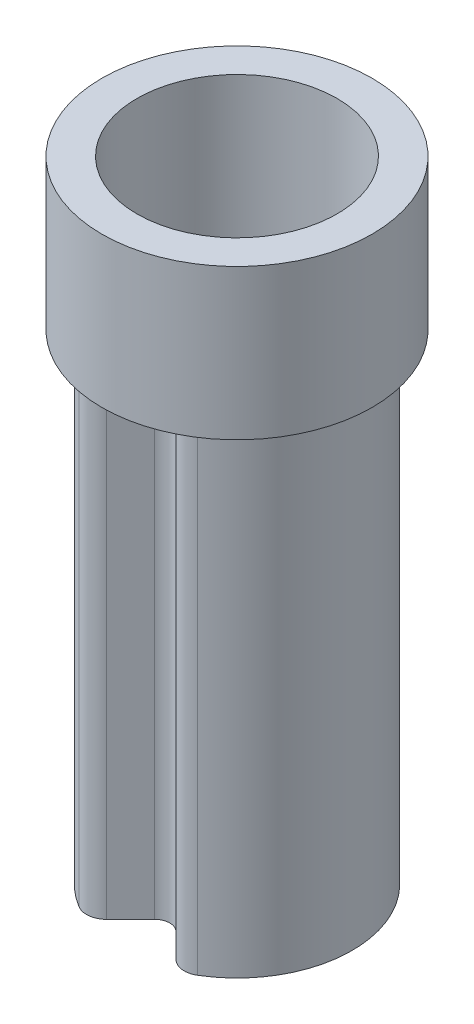
SolidWorks part; units mm, degrees
ref_plane "Front Plane" through (0, 0, 0) normal (0, 0, 1) x (1, 0, 0)
ref_plane "Top Plane" through (0, 0, 0) normal (0, 1, 0) x (1, 0, 0)
ref_plane "Right Plane" through (0, 0, 0) normal (1, 0, 0) x (0, 0, -1)
sketch "Sketch1" plane through (0, 0, 0) normal (0, 1, 0) x (1, 0, 0)
  line L0 (0, 0) -> (0, -1.15) construction
  line L1 (-0.4488, -1.0588) -> (-0.1061, -0.7161)
  line L2 (0.1061, -0.7161) -> (0.4488, -1.0588)
  line L3 (-0.4796, -0.8775) -> (-0.2121, -0.61)
  line L4 (0.2121, -0.61) -> (0.4796, -0.8775)
  arc A0 (0.4488, -1.0588) -> (-0.4488, -1.0588) centre (0, 0) ccw
  arc A1 (0.1061, -0.7161) -> (-0.1061, -0.7161) centre (0, -0.8221) ccw
  arc A2 (0.2121, -0.61) -> (-0.2121, -0.61) centre (0, -0.8221) ccw
  arc A3 (0.4796, -0.8775) -> (-0.4796, -0.8775) centre (0, 0) ccw
  point P8 (0, -0.61)
  dimension "D1" = 2.3
  dimension "D3" = 0.15
  dimension "D2" = 0.61
  dimension "D4" = 0.15
extrude "Boss-Extrude1" add sketch "Sketch1" along normal blind 4.8
fillet "Fillet1" radius 0.05 2 edges at (0.4796, 2.4, 0.8775) (-0.4796, 2.4, 0.8775)
fillet "Fillet2" radius 0.2 2 edges at (0.4488, 2.4, 1.0588) (-0.4488, 2.4, 1.0588)
sketch "Sketch2" plane through (0, 4.8, 0) normal (0, 1, 0) x (1, 0, 0)
  circle A0 centre (0, 0) radius 1.35
  circle A1 centre (0, 0) radius 1
  arc A2 (0.5136, -0.858) -> (-0.5136, -0.858) centre (0, 0) ccw construction
  dimension "D1" = 2.7
extrude "Boss-Extrude2" add sketch "Sketch2" along normal offset from surface (1.5 mm away) 6.3 up to face at (0, 0, 0.537)
